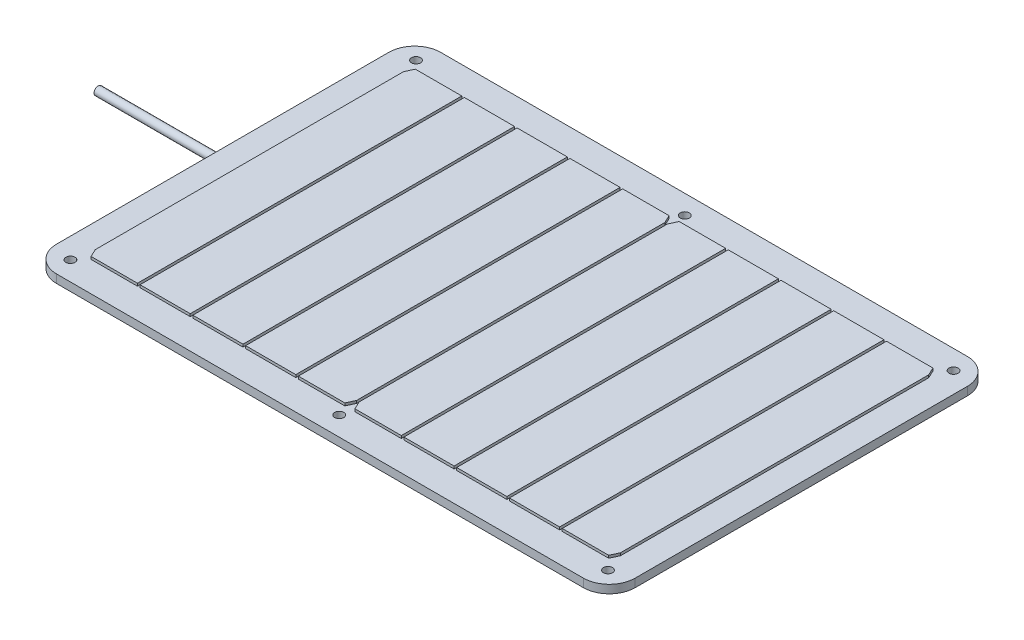
SolidWorks part; units mm, degrees
ref_plane "Front Plane" through (0, 0, 0) normal (0, 0, 1) x (1, 0, 0)
ref_plane "Top Plane" through (0, 0, 0) normal (0, 1, 0) x (1, 0, 0)
ref_plane "Right Plane" through (0, 0, 0) normal (1, 0, 0) x (0, 0, -1)
sketch "Sketch1" plane through (0, 0, 0) normal (0, 1, 0) x (1, 0, 0)
  line L1 (-101.5, 74) -> (101.5, 74)
  line L2 (-111.5, 64) -> (-111.5, -64)
  line L3 (-101.5, -74) -> (101.5, -74)
  line L4 (111.5, 64) -> (111.5, -64)
  arc A0 (101.5, 74) -> (111.5, 64) centre (101.5, 64) cw
  arc A1 (101.5, -74) -> (111.5, -64) centre (101.5, -64) ccw
  arc A2 (-111.5, -64) -> (-101.5, -74) centre (-101.5, -64) ccw
  arc A3 (-101.5, 74) -> (-111.5, 64) centre (-101.5, 64) ccw
  point P8 (111.5, -74)
  point P11 (-111.5, -74)
  point P14 (-111.5, 74)
  point P15 (-111.5, 0)
  point P17 (0, 74)
  dimension "D3" = 10
  dimension "D1" = 148
  dimension "D2" = 223
extrude "Boss-Extrude1" add sketch "Sketch1" along normal blind 3.2 contours L1 A0 L4 A1 L3 A2 L2 A3
sketch "Sketch2" plane through (0, 0, 0) normal (0, -1, 0) x (1, 0, 0)
  line L0 (-111.5, -64) -> (-111.5, 64) construction
  line L1 (-45, 15) -> (-25, 15)
  line L2 (-50, 10) -> (-50, -10)
  line L3 (-45, -15) -> (-25, -15)
  line L4 (-20, 10) -> (-20, -10)
  arc A0 (-25, 15) -> (-20, 10) centre (-25, 10) cw
  arc A1 (-25, -15) -> (-20, -10) centre (-25, -10) ccw
  arc A2 (-50, -10) -> (-45, -15) centre (-45, -10) ccw
  arc A3 (-45, 15) -> (-50, 10) centre (-45, 10) ccw
  point P6 (-20, 0)
  point P14 (-50, -15)
  point P17 (-50, 15)
  dimension "D3" = 5
  dimension "D1" = 30
  dimension "D2" = 61.5
extrude "Boss-Extrude2" add sketch "Sketch2" along normal blind 5
fillet "Fillet1" radius 5 8 edges at (-20, -5, 0) (-21.4645, -5, -13.5355) (-35, -5, -15) (-48.5355, -5, -13.5355) (-50, -5, 0) (-48.5355, -5, 13.5355) (-35, -5, 15) (-21.4645, -5, 13.5355)
sketch "Sketch3" plane through (-111.5, 0, 0) normal (-1, 0, 0) x (0, 0, 1)
  line L0 (-64, 0) -> (64, 0) construction
  circle A0 centre (0, -1.6) radius 1.6
  dimension "D1" = 3.2
extrude "Boss-Extrude5" add sketch "Sketch3" against normal blind 61.5 and the other way blind 48
sketch "Sketch4" plane through (0, 3.2, 0) normal (0, 1, 0) x (1, 0, 0)
  line L0 (-101.5, 74) -> (101.5, 74) construction
  line L1 (-111.5, 64) -> (-111.5, -64) construction
  circle A0 centre (-103.6, 66.6) radius 1.75
  circle A1 centre (0, 66.6) radius 1.75
  circle A2 centre (103.6, 66.6) radius 1.75
  circle A3 centre (0, -66.6) radius 1.75
  circle A4 centre (103.6, -66.6) radius 1.75
  circle A5 centre (-103.6, -66.6) radius 1.75
  dimension "D1" = 3.5
  dimension "D2" = 7.4
  dimension "D3" = 7.9
  dimension "D4" = 3
  dimension "D5" = 2
extrude "Cut-Extrude2" cut sketch "Sketch4" against normal through all
sketch "Sketch5" plane through (0, 3.2, 0) normal (0, 1, 0) x (1, 0, 0)
  line L6 (-60.52, 62.5) -> (-60.52, -62.5)
  line L7 (-99.7522, 62.5) -> (-101.2, 59.3952)
  line L8 (-101.2, 59.3952) -> (-101.2, -59.3952)
  line L9 (-101.2, -59.3952) -> (-99.7522, -62.5)
  line L10 (-99.7522, -62.5) -> (-81.86, -62.5)
  line L11 (-81.86, -62.5) -> (-81.86, 62.5)
  line L12 (-81.86, 62.5) -> (-99.7522, 62.5)
  line L13 (-111.5, 64) -> (-111.5, -64) construction
  line L14 (-101.5, -74) -> (101.5, -74) construction
  line L15 (-80.86, 62.5) -> (-61.52, 62.5)
  line L16 (-80.86, 62.5) -> (-80.86, -62.5)
  line L17 (-80.86, -62.5) -> (-61.52, -62.5)
  line L18 (-61.52, 62.5) -> (-61.52, -62.5)
  line L19 (-60.52, 62.5) -> (-41.18, 62.5)
  line L20 (-41.18, 62.5) -> (-41.18, -62.5)
  line L21 (-60.52, -62.5) -> (-41.18, -62.5)
  line L22 (-40.18, 62.5) -> (-40.18, -62.5)
  line L23 (-40.18, 62.5) -> (-20.84, 62.5)
  line L24 (-20.84, 62.5) -> (-20.84, -62.5)
  line L25 (-40.18, -62.5) -> (-20.84, -62.5)
  line L26 (-50.85, 49.4526) -> (-50.85, -36.6173) construction
  line L27 (-1.9478, -62.5) -> (-19.84, -62.5)
  line L28 (-0.5, -59.3952) -> (-1.9478, -62.5)
  line L29 (-0.5, 59.3952) -> (-0.5, -59.3952)
  line L30 (-19.84, -62.5) -> (-19.84, 62.5)
  line L31 (-19.84, 62.5) -> (-1.9478, 62.5)
  line L32 (-1.9478, 62.5) -> (-0.5, 59.3952)
  line L33 (41.18, 62.5) -> (41.18, -62.5)
  line L34 (1.9478, 62.5) -> (0.5, 59.3952)
  line L35 (0.5, 59.3952) -> (0.5, -59.3952)
  line L36 (0.5, -59.3952) -> (1.9478, -62.5)
  line L37 (1.9478, -62.5) -> (19.84, -62.5)
  line L38 (19.84, -62.5) -> (19.84, 62.5)
  line L39 (19.84, 62.5) -> (1.9478, 62.5)
  line L40 (20.84, 62.5) -> (40.18, 62.5)
  line L41 (20.84, 62.5) -> (20.84, -62.5)
  line L42 (20.84, -62.5) -> (40.18, -62.5)
  line L43 (40.18, 62.5) -> (40.18, -62.5)
  line L44 (41.18, 62.5) -> (60.52, 62.5)
  line L45 (60.52, 62.5) -> (60.52, -62.5)
  line L46 (41.18, -62.5) -> (60.52, -62.5)
  line L47 (61.52, 62.5) -> (61.52, -62.5)
  line L48 (61.52, 62.5) -> (80.86, 62.5)
  line L49 (80.86, 62.5) -> (80.86, -62.5)
  line L50 (61.52, -62.5) -> (80.86, -62.5)
  line L51 (99.7522, -62.5) -> (81.86, -62.5)
  line L52 (101.2, -59.3952) -> (99.7522, -62.5)
  line L53 (101.2, 59.3952) -> (101.2, -59.3952)
  line L54 (81.86, -62.5) -> (81.86, 62.5)
  line L55 (81.86, 62.5) -> (99.7522, 62.5)
  line L56 (99.7522, 62.5) -> (101.2, 59.3952)
  line L57 (50.85, 49.4526) -> (50.85, -36.6173) construction
  circle A0 centre (-103.6, 66.6) radius 1.75 construction
  circle A2 centre (-103.6, -66.6) radius 1.75 construction
  dimension "D3" = 25
  dimension "D1" = 19.34
  dimension "D2" = 125
  dimension "D4" = 10.3
  dimension "D5" = 11.5
  dimension "D6" = 5.22
  dimension "D7" = 5.22
  dimension "D8" = 19.34
  dimension "D9" = 125
  dimension "D10" = 1
  dimension "D11" = 11.5
  dimension "D13" = 9.67
  dimension "D12" = 3
  dimension "D14" = 2
extrude "Boss-Extrude6" add sketch "Sketch5" along normal blind 1
